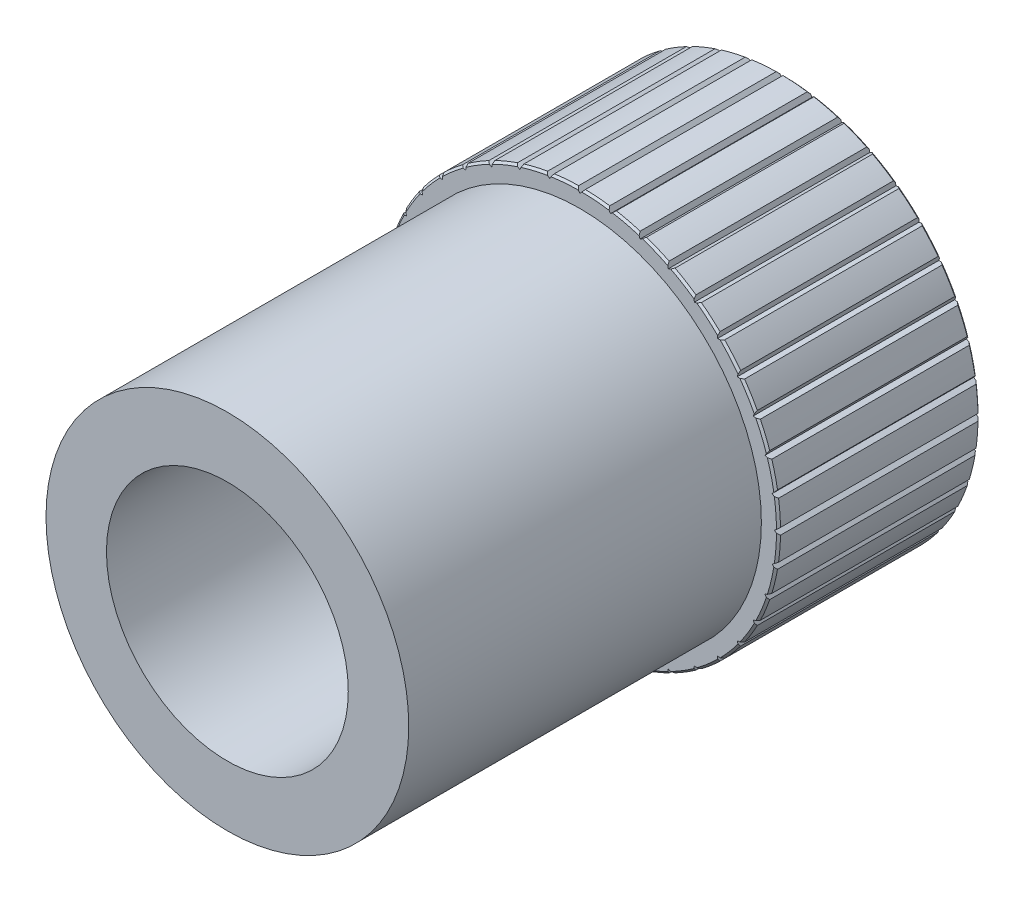
SolidWorks part; units mm, degrees
material "AISI 316 Annealed Stainless Steel Bar (SS)"
ref_plane "Front Plane" through (0, 0, 0) normal (0, 0, 1) x (1, 0, 0)
ref_plane "Top Plane" through (0, 0, 0) normal (0, 1, 0) x (1, 0, 0)
ref_plane "Right Plane" through (0, 0, 0) normal (1, 0, 0) x (0, 0, -1)
sketch "Sketch1" plane through (0, 0, 0) normal (0, 0, 1) x (1, 0, 0)
  circle A0 centre (0, 0) radius 6
  circle A1 centre (0, 0) radius 9
  circle A2 centre (0, 0) radius 9.85
  dimension "D1" = 12
  dimension "D2" = 18
  dimension "D3" = 19.7
extrude "Boss-Extrude1" add sketch "Sketch1" along normal blind 27.5 contours A1 A0 region at (-8.7454, 0, 0)
extrude "Boss-Extrude2" add sketch "Sketch1<3>" along normal blind 10 contours A2 A1 region at (-9.5714, 0, 0)
sketch "Sketch1<3>" plane through (0, 0, 0) normal (0, 0, 1) x (1, 0, 0) same geometry as "Sketch1"
sketch "Sketch2" plane through (0, 0, 0) normal (0, 0, -1) x (-1, 0, 0)
  line L0 (0, 0) -> (0, 9.85) construction
  line L1 (-0.8391, 10.65) -> (0.8391, 10.65)
  line L2 (0.8391, 10.65) -> (0, 9.65)
  line L3 (0, 9.65) -> (-0.8391, 10.65)
  circle A0 centre (0, 0) radius 7.5
  circle A1 centre (0, 0) radius 9.85
  circle A2 centre (0, 0) radius 9.85 construction
  circle M3 centre (0, 0) radius 6
  circle M4 centre (0, 0) radius 9.85
  dimension "D2" = 15
  dimension "D3" = 0.2
  dimension "D4" = 1
  dimension "D5" = 50
  dimension "D1" = 0
extrude "Cut-Extrude1" cut sketch "Sketch2" against normal blind 7.5 contours A0 M3 region at (7.2879, 0, 0)
extrude "Cut-Extrude2" cut sketch "Sketch2<3>" against normal up to surface (10 mm away) contours L3 L2 M4 | L3 L2 L1 M4 region at (0, 10.3388, 0) region at (0, 9.783, 0) up to face at (9, 0, 10)
sketch "Sketch2<3>" plane through (0, 0, 0) normal (0, 0, -1) x (-1, 0, 0) same geometry as "Sketch2"
chamfer "Chamfer1" distance 0.1 angle 45 2 edges at (0, -9.85, 10) (0, -9.85, 0)
pattern_circular "CirPattern1" count 40 over 360 about axis through (0, 0, 27.5) along (0, 0, -1) of "Cut-Extrude2" reverse direction yes
